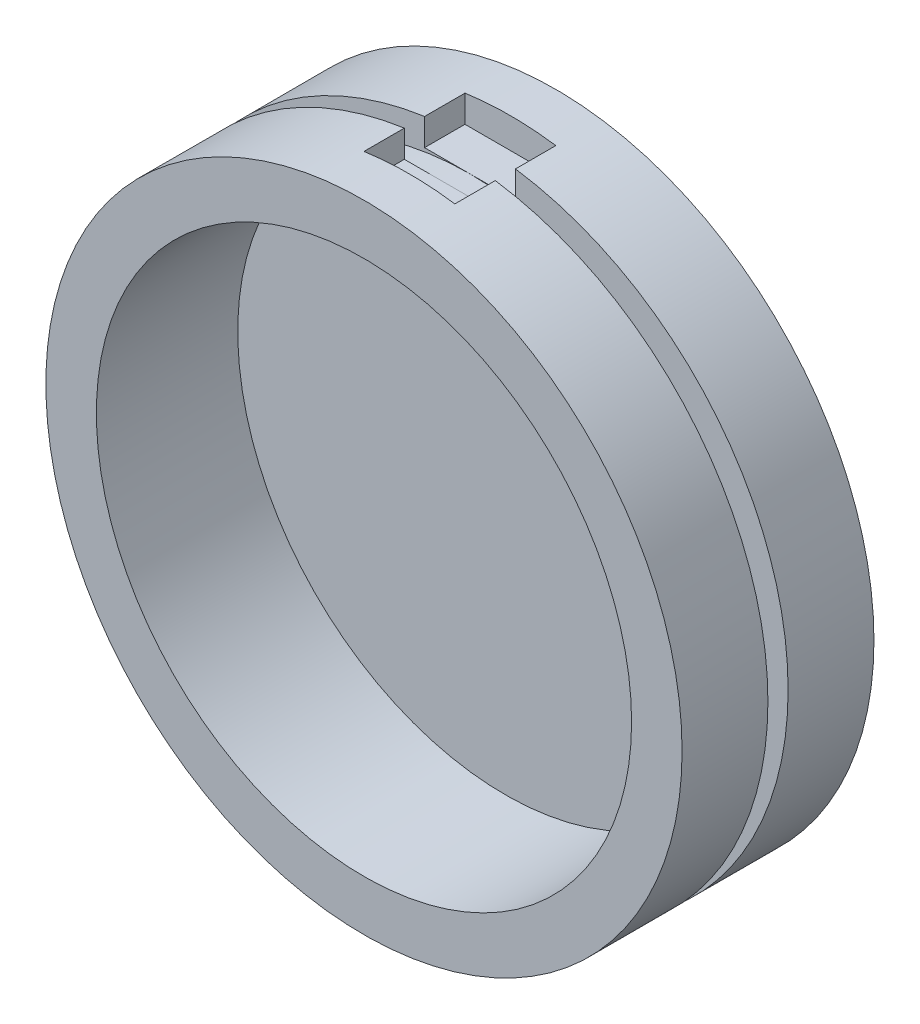
SolidWorks part; units mm, degrees
ref_plane "Front Plane" through (0, 0, 0) normal (0, 0, 1) x (1, 0, 0)
ref_plane "Top Plane" through (0, 0, 0) normal (0, 1, 0) x (1, 0, 0)
ref_plane "Right Plane" through (0, 0, 0) normal (1, 0, 0) x (0, 0, -1)
sketch "Sketch2" plane through (0, 0, 0) normal (1, 0, 0) x (0, 0, -1)
  line L0 (0, 0) -> (0, 31.5)
  line L1 (0, 31.5) -> (-8.5, 31.5)
  line L2 (-19, 31.5) -> (-19, 26.5)
  line L3 (-19, 26.5) -> (-5, 26.5)
  line L4 (-5, 26.5) -> (-5, 0)
  line L5 (-5, 0) -> (0, 0)
  line L6 (-8.5, 31.5) -> (-8.5, 28.5)
  line L7 (-8.5, 28.5) -> (-10.5, 28.5)
  line L8 (-10.5, 28.5) -> (-10.5, 31.5)
  line L9 (-10.5, 31.5) -> (-19, 31.5)
  dimension "D1" = 19
  dimension "D2" = 31.5
  dimension "D3" = 5
  dimension "D4" = 5
  dimension "D5" = 2
  dimension "D6" = 8.5
  dimension "D7" = 3
revolve "Revolve1" add sketch "Sketch2" angle 360 about L5
ref_plane "Plane1" through (0, 31.5, 0) normal (0, 1, 0) x (1, 0, 0)
sketch "Sketch7" plane through (0, 31.5, 0) normal (0, 1, 0) x (1, 0, 0)
  line L1 (-4.5, -14.5) -> (4.5, -14.5)
  line L2 (-4.5, -14.5) -> (-4.5, -4.5)
  line L3 (-4.5, -4.5) -> (4.5, -4.5)
  line L4 (4.5, -14.5) -> (4.5, -4.5)
  line L5 (-4.5, -9.5) -> (4.5, -9.5) construction
  line L6 (31.5, 0) -> (-31.5, 0) construction
  line L7 (0, -4.5) -> (0, 0) construction
  dimension "D1" = 9.5
  dimension "D2" = 10
  dimension "D3" = 9
extrude "Cut-Extrude1" cut sketch "Sketch7" against normal blind 3
mirror "Mirror1" about plane through (0, 0, 0) normal (0, 1, 0) of "Cut-Extrude1"
